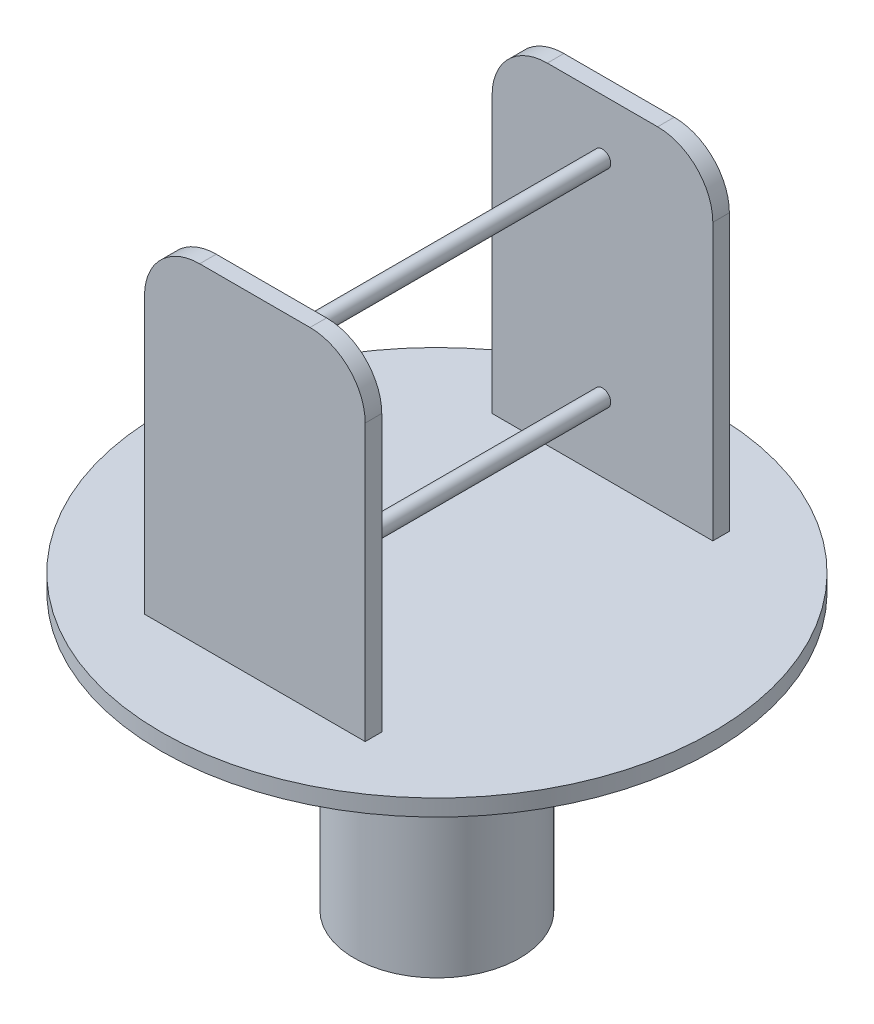
SolidWorks part; units mm, degrees
material "ENPH 253 Hardboard"
ref_plane "Front Plane" through (0, 0, 0) normal (0, 0, 1) x (1, 0, 0)
ref_plane "Top Plane" through (0, 0, 0) normal (0, 1, 0) x (1, 0, 0)
ref_plane "Right Plane" through (0, 0, 0) normal (1, 0, 0) x (0, 0, -1)
sketch "Sketch1" plane through (0, 0, 0) normal (0, 1, 0) x (1, 0, 0)
  circle A0 centre (0, 0) radius 50
  dimension "D1" = 100
extrude "Boss-Extrude1" add sketch "Sketch1" along normal blind 3
sketch "Sketch2" plane through (0, 0, 0) normal (0, -1, 0) x (-1, 0, 0)
  circle A0 centre (0, 0) radius 15
  dimension "D1" = 30
extrude "Boss-Extrude2" add sketch "Sketch2" along normal blind 50
sketch "Sketch3" plane through (0, 3, 0) normal (0, 1, 0) x (1, 0, 0)
  line L1 (-20, -33) -> (20, -33)
  line L2 (-20, -33) -> (-20, -30)
  line L3 (-20, -30) -> (20, -30)
  line L4 (20, -33) -> (20, -30)
  line L5 (-20, 30) -> (20, 30)
  line L6 (-20, 30) -> (-20, 33)
  line L7 (-20, 33) -> (20, 33)
  line L8 (20, 30) -> (20, 33)
  dimension "D1" = 40
  dimension "D2" = 3
  dimension "D5" = 30
  dimension "D6" = 30
  dimension "D7" = 20
  dimension "D3" = 20
extrude "Boss-Extrude3" add sketch "Sketch3" along normal blind 60
sketch "Sketch4" plane through (0, 0, 33) normal (0, 0, 1) x (1, 0, 0)
  line L2 (-20, 3) -> (20, 3) construction
  circle A0 centre (0, 53) radius 1.5
  circle A1 centre (0, 53) radius 30 construction
  circle A2 centre (0, 15.5) radius 1.5
  circle A3 centre (0, 15.5) radius 7.5 construction
  dimension "D1" = 3
  dimension "D2" = 50
  dimension "D3" = 60
  dimension "D4" = 3
  dimension "D5" = 15
extrude "Boss-Extrude4" add sketch "Sketch4" against normal up to surface (63 mm away) contours A0 | A2 up to face at (0, 33, -30)
fillet "Fillet1" radius 10 4 edges at (-20, 63, 31.5) (-20, 63, -31.5) (20, 63, -31.5) (20, 63, 31.5)
equation "\"D7@Sketch3\"=\"D1@Sketch3\"/2"
equation "\"D3@Sketch3\"=\"D7@Sketch3\""
